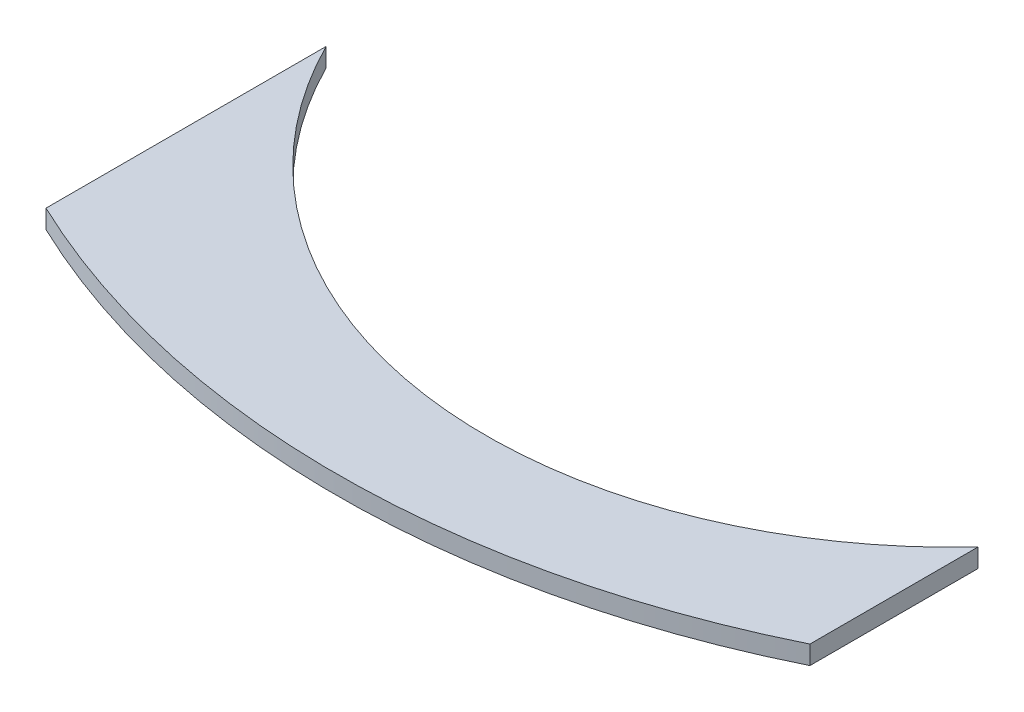
SolidWorks part; units mm, degrees
material "1023 Chapa de acero al carbono (SS)"
ref_plane "Alzado" through (0, 0, 0) normal (0, 0, 1) x (1, 0, 0)
ref_plane "Planta" through (0, 0, 0) normal (0, 1, 0) x (1, 0, 0)
ref_plane "Vista lateral" through (0, 0, 0) normal (1, 0, 0) x (0, 0, -1)
sketch "Sketch1" plane through (0, 0, 0) normal (0, 1, 0) x (1, 0, 0)
  line L0 (0, 22.5) -> (0, -22.5)
  line L1 (122, 5.2144) -> (122, -21.7856)
  arc A0 (0, 22.5) -> (122, 5.2144) centre (67, 56.2046) ccw
  arc A1 (0, -22.5) -> (122, -21.7856) centre (60.2621, 103.8664) ccw
  point P8 (0, 0)
  dimension "D3" = 75
  dimension "D6" = 140
  dimension "D1" = 45
  dimension "D2" = 27
  dimension "D4" = 55
  dimension "D5" = 122
base flange "Base-Flange1" sketch "Sketch1" thickness 3 reverse thickness direction no parameters "D1"=0.7366
sketch "Sketch3" [suppressed] plane through (0, 0, 0) normal (0, 1, 0) x (1, 0, 0)
sketch "Sketch5" [suppressed] plane through (0, 0, 0) normal (0, 1, 0) x (1, 0, 0)
sheet metal parameters "Sheet-Metal1" thickness 3 parameters "D1"=0.7366
flat pattern "Flat-Pattern1" [suppressed]
sketch "Sketch7" plane through (0, 0, 0) normal (0, 1, 0) x (1, 0, 0)
sketch3d "Sketch9" [suppressed]
  line L0 (-74.1523, -84.1848, 0) -> (51.5979, -102.0017, 0) construction
  line L1 (-67, -33.7046, 0) -> (58.7502, -51.5215, 0) construction
  line L2 (-74.1523, -84.1848, 0) -> (-67, -33.7046, 0) construction
  line L3 (51.5979, -102.0017, 0) -> (58.7502, -51.5215, 0) construction
